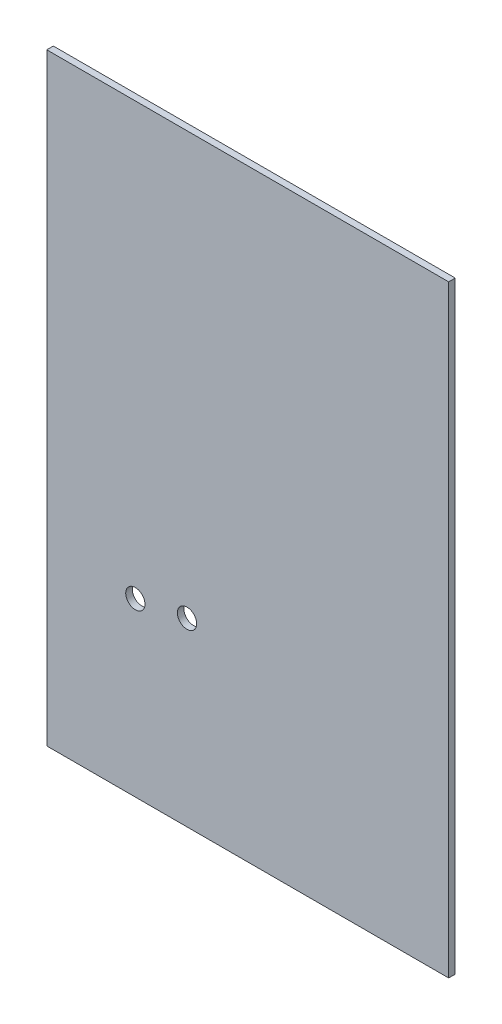
SolidWorks part; units mm, degrees
material "Polypropylene"
ref_plane "Front Plane" through (0, 0, 0) normal (0, 0, 1) x (1, 0, 0)
ref_plane "Top Plane" through (0, 0, 0) normal (0, 1, 0) x (1, 0, 0)
ref_plane "Right Plane" through (0, 0, 0) normal (1, 0, 0) x (0, 0, -1)
sketch "Sketch1" plane through (0, 0, 0) normal (0, 0, 1) x (1, 0, 0)
  line L1 (0, 0) -> (292.1, 0)
  line L2 (0, 0) -> (0, -438.15)
  line L3 (0, -438.15) -> (292.1, -438.15)
  line L4 (292.1, 0) -> (292.1, -438.15)
  line L5 (64.3744, -313.2564) -> (101.9257, -306.8134) construction
  line L6 (64.3744, -313.2564) -> (101.9257, -313.2564) construction
  line L7 (101.9257, -313.2564) -> (101.9257, -306.8134) construction
  circle A0 centre (101.9257, -306.8134) radius 7
  circle A1 centre (64.3744, -313.2564) radius 7
  dimension "D3" = 14
  dimension "D1" = 438.15
  dimension "D2" = 292.1
  dimension "D4" = 38.1
  dimension "D5" = 9.736
extrude "Boss-Extrude1" add sketch "Sketch1" along normal blind 4.7625
